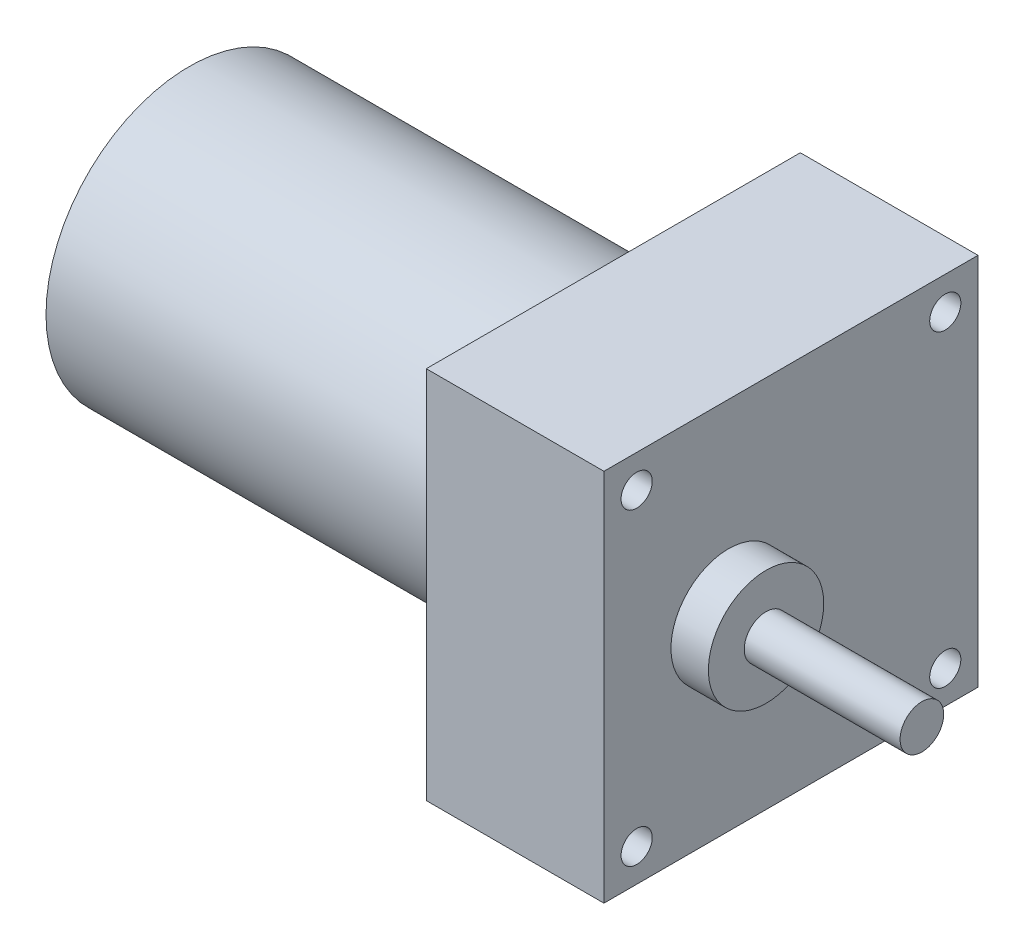
SolidWorks part; units mm, degrees
ref_plane "Front Plane" through (0, 0, 0) normal (1, 0, 0) x (0, 1, 0)
ref_plane "Top Plane" through (0, 0, 0) normal (0, 0, 1) x (0, 1, 0)
ref_plane "Right Plane" through (0, 0, 0) normal (0, 1, 0) x (-1, 0, 0)
sketch "Sketch1" plane through (0, 0, 0) normal (1, 0, 0) x (0, 1, 0)
  line L0 (0, 0) -> (0, -13.4172) construction
  line L1 (-30, -30) -> (30, -30)
  line L2 (-30, -30) -> (-30, 30)
  line L3 (-30, 30) -> (30, 30)
  line L4 (30, -30) -> (30, 30)
  line L5 (-30, -30) -> (30, 30) construction
  line L6 (-30, 30) -> (30, -30) construction
  line L7 (55, 0) -> (-55, 0) construction
  circle A0 centre (-24.75, 24.75) radius 2.5
  circle A1 centre (24.75, 24.75) radius 2.5
  circle A2 centre (24.75, 24.75) radius 2.5
  circle A3 centre (24.75, -24.75) radius 2.5
  circle A4 centre (-24.75, -24.75) radius 2.5
  circle A5 centre (0, 10) radius 3.5
  circle A6 centre (0, 10) radius 9.25
  point P0 (0, 0)
  point P22 (0, 0)
  dimension "D2" = 5
  dimension "D4" = 7
  dimension "D5" = 18.5
  dimension "D1" = 60
  dimension "D3" = 49.5
  dimension "D6" = 10
extrude "Boss-Extrude1" add sketch "Sketch1" along normal blind 28.5 contours L1 L4 L3 L2 A1 A0 A3 A4 | A6 A5 | A5 region at (0, 0, -0.8264) region at (0, 0, 10) region at (0, -8.9884, 10)
extrude "Boss-Extrude2" add sketch "Sketch1<3>" along normal blind 6 from surface contours A6 A5 region at (0, -8.9884, 10) starting at face at (28.5, 24.75, 22.25)
sketch "Sketch1<3>" plane through (0, 0, 0) normal (1, 0, 0) x (0, 1, 0) same geometry as "Sketch1"
extrude "Boss-Extrude3" add sketch "Sketch1<4>" along normal blind 25 from surface separate body contours A5 region at (0, 0, 10) starting at face at (34.5, 0, 0.75)
sketch "Sketch1<4>" plane through (0, 0, 0) normal (1, 0, 0) x (0, 1, 0) same geometry as "Sketch1"
sketch "Sketch2" plane through (0, 0, 0) normal (-1, 0, 0) x (0, -1, 0)
  circle A0 centre (0, 0) radius 23
  dimension "D1" = 46
extrude "Boss-Extrude4" add sketch "Sketch2" along normal blind 68
